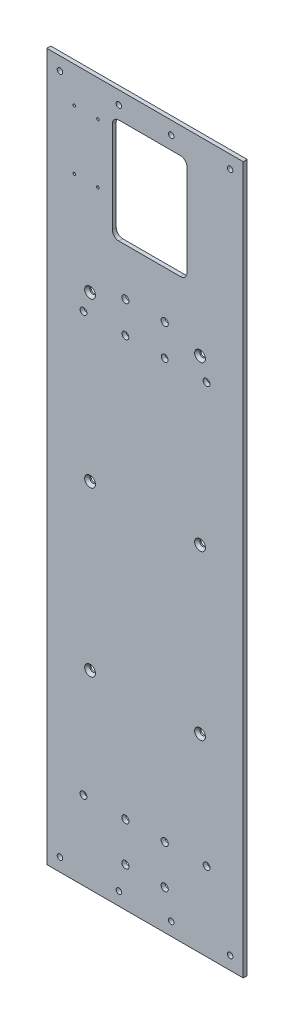
SolidWorks part; units mm, degrees
material "Thornel Mat VMA"
ref_plane "Front" through (0, 0, 0) normal (0, 0, 1) x (1, 0, 0)
ref_plane "Top" through (0, 0, 0) normal (0, 1, 0) x (1, 0, 0)
ref_plane "Right" through (0, 0, 0) normal (1, 0, 0) x (0, 0, -1)
sketch "草图1" plane through (0, 0, 0) normal (0, 0, 1) x (1, 0, 0)
  line L1 (-75, -270) -> (75, -270)
  line L2 (-75, -270) -> (-75, 270)
  line L3 (-75, 270) -> (75, 270)
  line L4 (75, -270) -> (75, 270)
  line L5 (-75, -270) -> (75, 270) construction
  line L6 (-75, 270) -> (75, -270) construction
  point P0 (0, 0)
  dimension "D1" = 150
  dimension "D2" = 540
extrude "凸台-拉伸1" add sketch "草图1" along normal blind 3
sketch "草图2" plane through (0, 0, 0) normal (0, 0, -1) x (-1, 0, 0)
  line L0 (-75, 0) -> (75, 0) construction
  line L1 (-75, -270) -> (-75, 270) construction
  line L2 (75, 270) -> (75, -270) construction
  line L3 (75, -270) -> (-75, -270) construction
  line L4 (0, -270) -> (0, -312.3628) construction
  line L5 (0, 270) -> (0, 297.7999) construction
  line L6 (-75, 270) -> (75, 270) construction
  circle A2 centre (65, -260) radius 2.1
  circle A3 centre (-65, -260) radius 2.1
  circle A6 centre (65, 260) radius 2.1
  circle A7 centre (-65, 260) radius 2.1
  circle A8 centre (-20, -260) radius 2.1
  circle A9 centre (20, -260) radius 2.1
  circle A10 centre (20, 260) radius 2.1
  circle A11 centre (-20, 260) radius 2.1
  circle A16 centre (15, 196.5) radius 1.6
  circle A17 centre (15, 188.5) radius 1.6
  circle A18 centre (-15, 196.5) radius 1.6
  circle A19 centre (-15, 188.5) radius 1.6
  dimension "D1" = 45
  dimension "D2" = 45
  dimension "D3" = 3.2
  dimension "D4" = 4.2
  dimension "D5" = 10
  dimension "D6" = 10
  dimension "D7" = 4.2
  dimension "D8" = 10
  dimension "D9" = 10
  dimension "D10" = 30
  dimension "D11" = 8
  dimension "D12" = 73.5
extrude "切除-拉伸1" cut sketch "草图2" against normal through all
sketch "草图3" plane through (0, 0, 3) normal (0, 0, 1) x (1, 0, 0)
  line L1 (75, -270) -> (75, 270) construction
  circle A0 centre (65, 30) radius 1.5
  circle A1 centre (65, -30) radius 1.5
  dimension "D1" = 3
  dimension "D2" = 10
  dimension "D3" = 30
  dimension "D4" = 3
  dimension "D5" = 30
  dimension "D6" = 10
sketch "草图4" plane through (0, 0, 3) normal (0, 0, 1) x (1, 0, 0)
  line L0 (42, 0) -> (140.7159, 0) construction
  line L1 (75, -270) -> (75, 270) construction
  line L2 (0, 270) -> (0, -270) construction
  line L3 (75, 270) -> (-75, 270) construction
  line L4 (-75, -270) -> (75, -270) construction
  line L5 (-42, 0) -> (-140.7159, 0) construction
  circle A0 centre (42, 125) radius 2.1
  circle A1 centre (42, -125) radius 2.1
  circle A2 centre (42, 0) radius 2.1
  circle A3 centre (-42, 0) radius 2.1
  circle A4 centre (-42, -125) radius 2.1
  circle A5 centre (-42, 125) radius 2.1
  dimension "D1" = 250
  dimension "D2" = 4.2
  dimension "D3" = 4.2
  dimension "D4" = 33
  dimension "D5" = 33
extrude "切除-拉伸2" cut sketch "草图4" against normal up to next
chamfer "倒角1" distance 2 angle 45 3 edges at (44.1, 0, 3) (39.9, -125, 3) (44.1, 125, 3)
sketch "草图6" plane through (0, 0, 3) normal (0, 0, 1) x (1, 0, 0)
  line L0 (0, -286.6484) -> (0, 69.1326) construction
  line L1 (-75, -270) -> (75, -270) construction
  line L2 (-75, 270) -> (-75, -270) construction
  line L3 (75, -270) -> (75, 270) construction
  line L6 (75, 270) -> (-75, 270) construction
  circle A1 centre (15, -210) radius 2.6
  circle A4 centre (-15, -210) radius 2.6
  circle A5 centre (47, -210) radius 2.6
  circle A6 centre (-47, -210) radius 2.6
  circle A9 centre (-47, 110) radius 2.6
  circle A10 centre (-15, 110.0003) radius 2.6
  circle A11 centre (15, 110.0005) radius 2.6
  circle A12 centre (47, 110.0006) radius 2.6
  dimension "D1" = 5.2
  dimension "D2" = 15
  dimension "D3" = 60
  dimension "D4" = 32
  dimension "D5" = 5.2
  dimension "D6" = 5.2
  dimension "D7" = 5.2
  dimension "D8" = 5.2
  dimension "D9" = 32
  dimension "D10" = 30
  dimension "D11" = 32
  dimension "D12" = 28
  dimension "D13" = 28
  dimension "D14" = 160
extrude "切除-拉伸4" cut sketch "草图6" against normal up to next
sketch "草图7" plane through (0, 0, 3) normal (0, 0, 1) x (1, 0, 0)
  line L4 (75, -270) -> (75, 270)
  line L5 (75, 270) -> (-75, 270)
  line L6 (-75, 270) -> (-75, -270)
  line L7 (-75, -270) -> (75, -270)
  line L8 (75, -270) -> (75, 270)
  line L9 (75, 270) -> (-75, 270)
  line L10 (-75, 270) -> (-75, -270)
  line L11 (-75, -270) -> (75, -270)
  circle A2 centre (-15, 134) radius 2.75
  circle A3 centre (15, 134) radius 2.75
  dimension "D2" = 136
  dimension "D3" = 5.5
  dimension "D5" = 30
  dimension "D6" = 5.5
  dimension "D7" = 60
  dimension "D4" = 136
  dimension "D1" = 0
extrude "切除-拉伸5" cut sketch "草图7" against normal up to next contours A2 | A3 region at (-15, 134, 3)
sketch "草图8" plane through (0, 0, 3) normal (0, 0, 1) x (1, 0, 0)
  line L4 (75, -270) -> (75, 270)
  line L5 (75, 270) -> (-75, 270)
  line L6 (-75, 270) -> (-75, -270)
  line L7 (-75, -270) -> (75, -270)
  line L8 (75, -270) -> (75, 270)
  line L9 (75, 270) -> (-75, 270)
  line L10 (-75, 270) -> (-75, -270)
  line L11 (-75, -270) -> (75, -270)
  circle A2 centre (-15, -210) radius 2.75
  circle A3 centre (15, -210) radius 2.75
  dimension "D2" = 5.5
  dimension "D3" = 5.5
  dimension "D4" = 30
  dimension "D5" = 60
  dimension "D6" = 60
  dimension "D7" = 60
  dimension "D1" = 0
extrude "切除-拉伸6" cut sketch "草图8" against normal up to next contours A2 | A3 region at (-15, -210, 3) region at (15, -210, 3)
sketch "草图9" plane through (0, 0, 3) normal (0, 0, 1) x (1, 0, 0)
  line L0 (0, -270) -> (0, -79.9483) construction
  line L1 (-75, -270) -> (75, -270) construction
  circle A0 centre (-15, -240) radius 2.75
  circle A1 centre (15, -240) radius 2.75
  dimension "D1" = 5.5
  dimension "D2" = 30
  dimension "D3" = 30
extrude "切除-拉伸7" cut sketch "草图9" against normal blind 10
sketch "草图10" plane through (0, 0, 3) normal (0, 0, 1) x (1, 0, 0)
  line L0 (0, 270) -> (0, 151.6479) construction
  line L1 (75, 270) -> (-75, 270) construction
  line L2 (-25, 170) -> (-25, 250)
  line L3 (-25, 170) -> (25, 170)
  line L4 (0, 170) -> (0, 250)
  line L5 (-25, 250) -> (25, 250)
  line L6 (25, 170) -> (25, 250)
  line L8 (25, 250) -> (32, 250)
  line L9 (25, 250) -> (25, 170)
  line L10 (25, 170) -> (32, 170)
  line L11 (32, 250) -> (32, 170)
  circle M23 centre (-15, 196.5) radius 1.6
  circle M28 centre (15, 188.5) radius 1.6
  circle M29 centre (15, 196.5) radius 1.6
  circle M30 centre (-15, 188.5) radius 1.6
  dimension "D1" = 50
  dimension "D2" = 20
  dimension "D3" = 80
  dimension "D4" = 7
extrude "切除-拉伸8" cut sketch "草图10" against normal blind 10 contours L5 L2 L3 L4 M30 M23 | L3 L6 L5 L4 M28 M29 | L11 L8 L6 L10 region at (-12.4797, 210.1419, 3) region at (12.4797, 210.1419, 3) region at (28.5, 210, 3)
fillet "圆角1" radius 5 4 edges at (-25, 170, 1.5) (-25, 250, 1.5) (32, 170, 1.5) (32, 250, 1.5)
chamfer "倒角2" distance 2 angle 45 3 edges at (-39.9, -125, 3) (-44.1, 0, 3) (-44.1, 125, 3)
sketch "草图11" plane through (0, 0, 3) normal (0, 0, 1) x (1, 0, 0)
  line L0 (-45, 266.5246) -> (-45, 192.9358) construction
  line L1 (-66.7226, 220) -> (-27.8973, 220) construction
  line L2 (-75, 270) -> (-75, -270) construction
  line L3 (75, 270) -> (-75, 270) construction
  circle A0 centre (-54, 242.6) radius 1
  circle A1 centre (-36, 242.6) radius 1
  circle A2 centre (-36, 197.4) radius 1
  circle A3 centre (-54, 197.4) radius 1
  dimension "D1" = 2
  dimension "D2" = 18
  dimension "D3" = 45.2
  dimension "D4" = 30
  dimension "D5" = 50
extrude "切除-拉伸9" cut sketch "草图11" against normal blind 4
